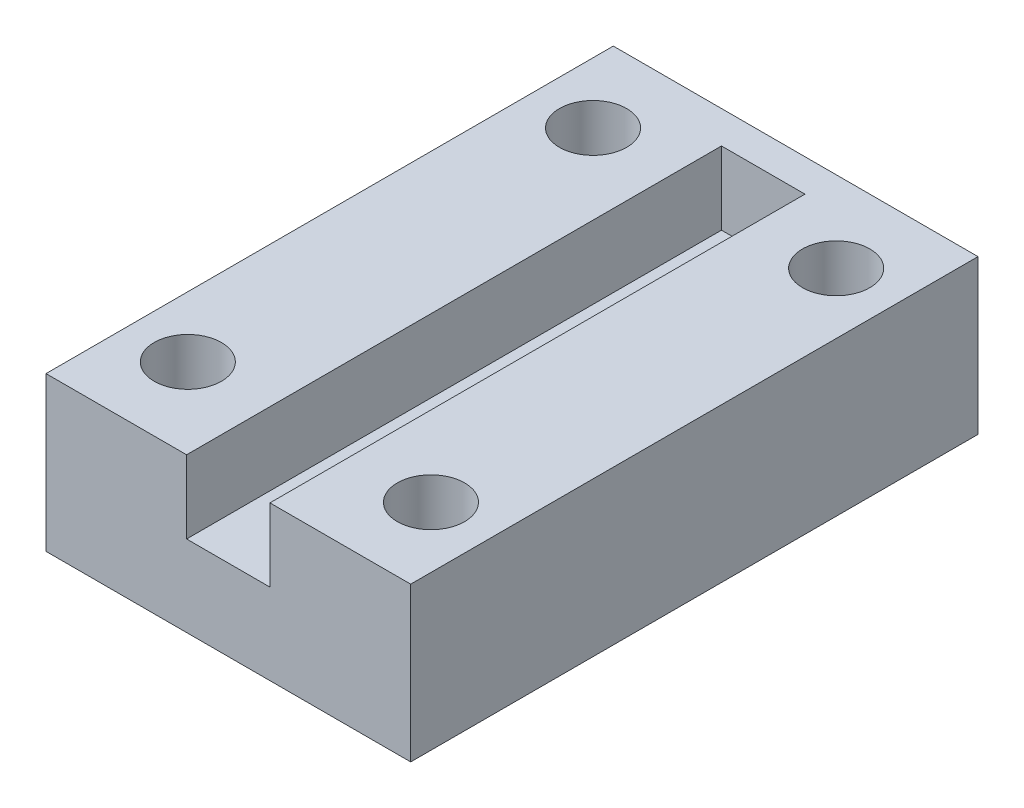
SolidWorks part; units mm, degrees
ref_plane "Спереди" through (0, 0, 0) normal (0, 0, 1) x (1, 0, 0)
ref_plane "Сверху" through (0, 0, 0) normal (0, 1, 0) x (1, 0, 0)
ref_plane "Справа" through (0, 0, 0) normal (1, 0, 0) x (0, 0, -1)
sketch "Sketch1" plane through (0, 0, 0) normal (0, 1, 0) x (1, 0, 0)
  line L1 (22.5, -35) -> (-22.5, -35)
  line L2 (22.5, -35) -> (22.5, 35)
  line L3 (22.5, 35) -> (-22.5, 35)
  line L4 (-22.5, -35) -> (-22.5, 35)
  line L5 (22.5, -35) -> (-22.5, 35) construction
  line L6 (22.5, 35) -> (-22.5, -35) construction
  point P0 (0, 0)
  dimension "D1" = 45
  dimension "D2" = 70
extrude "Boss-Extrude1" add sketch "Sketch1" along normal blind 10
sketch "Sketch3" plane through (0, 0, 0) normal (0, -1, 0) x (1, 0, 0)
  line L0 (15, -25) -> (15, 25) construction
  line L1 (-15, 25) -> (-15, -25) construction
  line L2 (-15, -25) -> (15, 25) construction
  line L3 (-22.5, -25) -> (22.5, -25) construction
  line L4 (-22.5, -35) -> (-22.5, 35) construction
  line L5 (22.5, 35) -> (22.5, -35) construction
  line L6 (-22.5, 25) -> (22.5, 25) construction
  line L7 (-22.5, -35) -> (-22.5, 35) construction
  line L8 (22.5, 35) -> (22.5, -35) construction
  line L9 (-15, 25) -> (15, -25) construction
  circle A0 centre (15, 25) radius 4.15
  circle A1 centre (15, -25) radius 4.15
  circle A2 centre (-15, -25) radius 4.15
  circle A3 centre (-15, 25) radius 4.15
  point P4 (0, 0)
  dimension "D1" = 8.3
  dimension "D2" = 30
  dimension "D3" = 50
extrude "Cut-Extrude2" cut sketch "Sketch3" against normal through all
sketch "Sketch5" plane through (0, 10, 0) normal (0, 1, 0) x (1, 0, 0)
  line L0 (5.15, 35) -> (-5.15, -35) construction
  line L1 (-5.15, -35) -> (-22.5, -35)
  line L2 (-5.15, -35) -> (-5.15, 35) construction
  line L3 (-5.15, 35) -> (-22.5, 35) construction
  line L4 (-22.5, -35) -> (-22.5, 35)
  line L5 (-5.15, -35) -> (-22.5, 35) construction
  line L6 (-5.15, 35) -> (-22.5, -35) construction
  line L7 (5.15, -35) -> (22.5, -35)
  line L8 (5.15, -35) -> (5.15, 35) construction
  line L9 (5.15, 35) -> (22.5, 35) construction
  line L10 (22.5, -35) -> (22.5, 35)
  line L11 (5.15, -35) -> (22.5, 35) construction
  line L12 (5.15, 35) -> (22.5, -35) construction
  line L13 (5.15, -35) -> (-5.15, 35) construction
  line L14 (-5.15, -35) -> (-5.15, 31)
  line L15 (-5.15, 31) -> (5.15, 31)
  line L16 (5.15, 31) -> (5.1302, -34.9493)
  line L17 (5.15, -35) -> (5.1302, -34.9493)
  line L18 (-22.5, 35) -> (22.5, 35)
  circle A0 centre (-15, 25) radius 4.15
  circle A1 centre (15, 25) radius 4.15
  circle A2 centre (15, -25) radius 4.15
  circle A3 centre (-15, -25) radius 4.15
  point P0 (-13.825, 0)
  point P6 (13.825, 0)
  point P12 (0, 0)
  dimension "D1" = 10.3
  dimension "D2" = 4
extrude "Boss-Extrude2" add sketch "Sketch5" along normal blind 9
chamfer "Chamfer1" distance 1 angle 50 4 edges at (15, 0, 20.85) (-15, 0, 20.85) (-15, 0, -29.15) (15, 0, -29.15) first distance on face at (-15, 0, 20.85)
